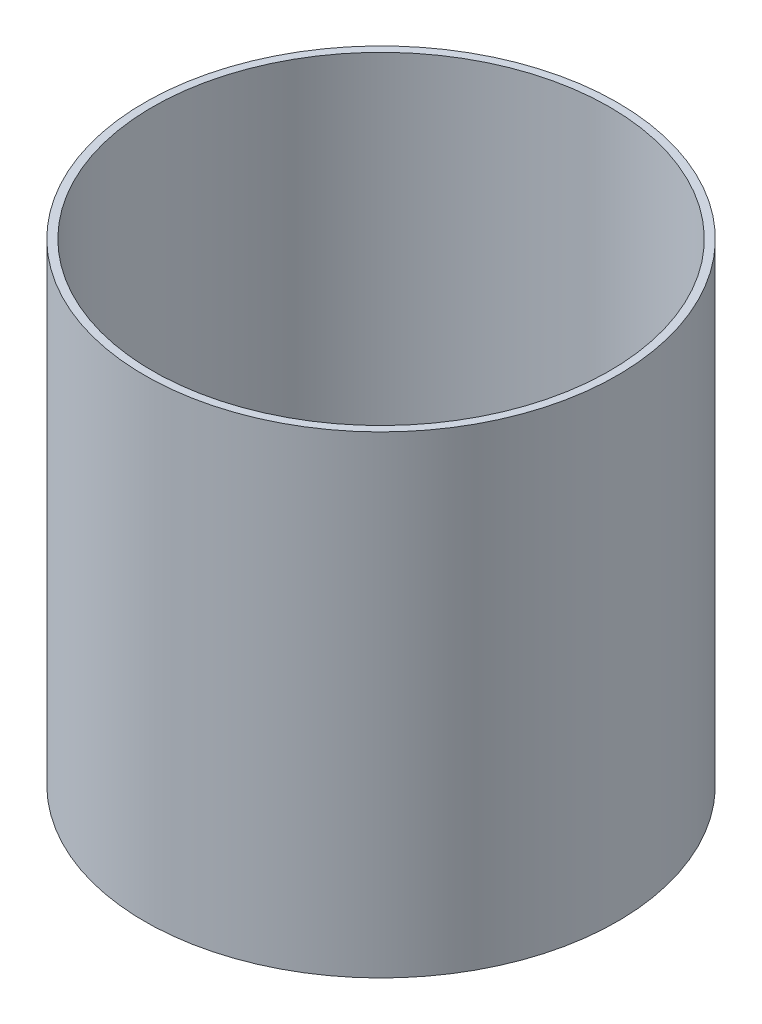
SolidWorks part; units mm, degrees
material "A-Glass Fiber"
ref_plane "Front Plane" through (0, 0, 0) normal (0, 0, 1) x (1, 0, 0)
ref_plane "Top Plane" through (0, 0, 0) normal (0, 1, 0) x (1, 0, 0)
ref_plane "Right Plane" through (0, 0, 0) normal (1, 0, 0) x (0, 0, -1)
sketch "Sketch1" plane through (0, 0, 0) normal (0, 1, 0) x (1, 0, 0)
  circle A0 centre (0, 0) radius 73.66
  circle A1 centre (0, 0) radius 76.1746
  dimension "D1" = 152.3492
  dimension "D2" = 147.32
extrude "Boss-Extrude1" add sketch "Sketch1" along normal blind 152.4
ref_plane "Plane1" through (0, 76.2, 0) normal (0, 1, 0) x (1, 0, 0)
equation "\"Length\"= 6"
equation "\"D1@Boss-Extrude1\"=\"Length\""
